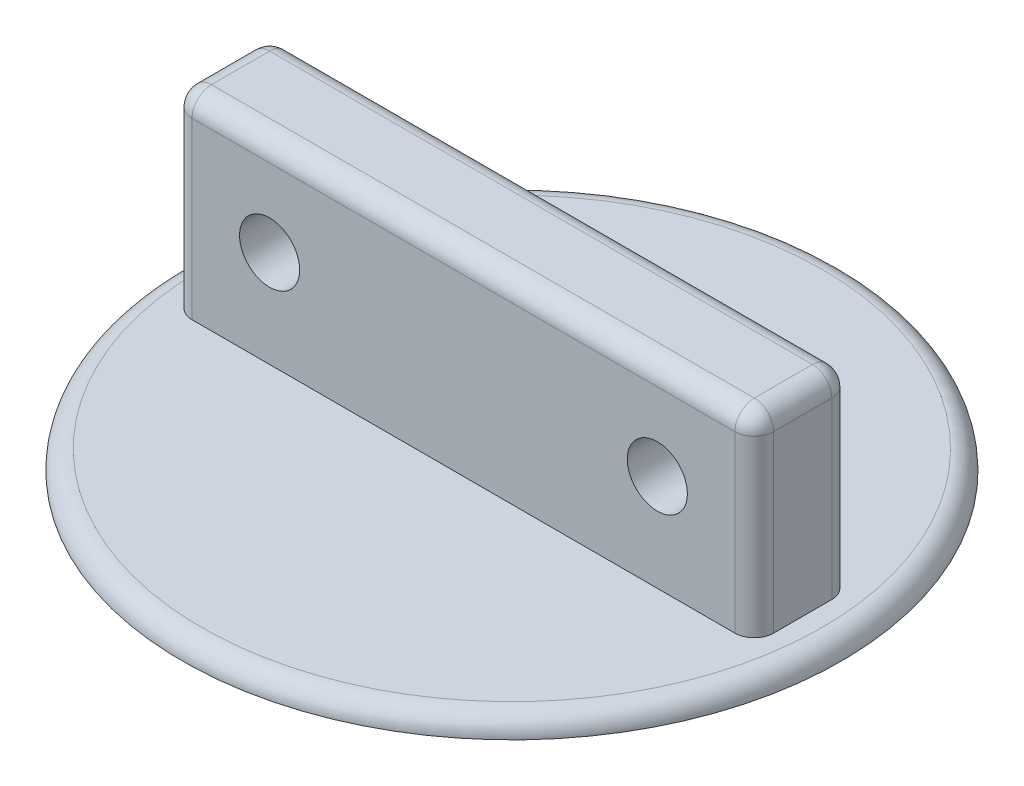
SolidWorks part; units mm, degrees
material "PET"
ref_plane "Front Plane" through (0, 0, 0) normal (0, 0, 1) x (1, 0, 0)
ref_plane "Top Plane" through (0, 0, 0) normal (0, 1, 0) x (1, 0, 0)
ref_plane "Right Plane" through (0, 0, 0) normal (1, 0, 0) x (0, 0, -1)
sketch "Sketch1" plane through (0, 0, 0) normal (0, 0, 1) x (1, 0, 0)
  line L1 (-38.1, 12.7) -> (38.1, 12.7)
  line L2 (-38.1, 12.7) -> (-38.1, -12.7)
  line L3 (-38.1, -12.7) -> (38.1, -12.7)
  line L4 (38.1, 12.7) -> (38.1, -12.7)
  line L5 (-38.1, 12.7) -> (38.1, -12.7) construction
  line L6 (-38.1, -12.7) -> (38.1, 12.7) construction
  point P0 (0, 0)
  dimension "D1" = 76.2
  dimension "D2" = 25.4
extrude "Boss-Extrude1" add sketch "Sketch1" along normal mid plane 12.7
fillet "Fillet1" radius 2.54 8 edges at (0, 12.7, -6.35) (-38.1, 0, -6.35) (38.1, 0, -6.35) (-38.1, 0, 6.35) (0, 12.7, 6.35) (38.1, 0, 6.35) (-38.1, 12.7, 0) (38.1, 12.7, 0)
hole_wizard "#97 (0.31) Diameter Hole1" positions "Sketch2" profile "Sketch3" hole size "#97" standard "ANSI Inch"
sketch "Sketch2" plane through (0, 0, 6.35) normal (0, 0, 1) x (1, 0, 0)
  line L2 (35.56, -12.7) -> (35.56, 10.16) construction
  point P0 (25.4, 0)
  point P2 (-25.4, 0)
  dimension "D1" = 50.8
  dimension "D2" = 10.16
sketch "Sketch3" plane through (25.4, 0, 6.35) normal (1, 0, 0) x (0, -1, 0)
  line L0 (0, 0) -> (0, 27.7656)
  line L1 (0, 27.7656) -> (3.937, 25.4)
  line L2 (3.937, 25.4) -> (3.937, 0)
  line L5 (3.937, 0) -> (0, 0)
  line L10 (0, 27.7656) -> (-3.937, 25.4) construction
  line L11 (0, -6.35) -> (0, 107.95) construction
  dimension "Hole Dia." = 7.874
  dimension "Hole Depth" = 25.4
  dimension "Drill Angle" = 118
sketch "Sketch4" plane through (0, -12.7, 0) normal (0, -1, 0) x (1, 0, 0)
  circle A0 centre (0, 0) radius 43.18
  dimension "D1" = 86.36
extrude "Boss-Extrude2" add sketch "Sketch4" along normal blind 2.54
fillet "Fillet2" radius 2.54 1 edges at (0, -12.7, -43.18)
